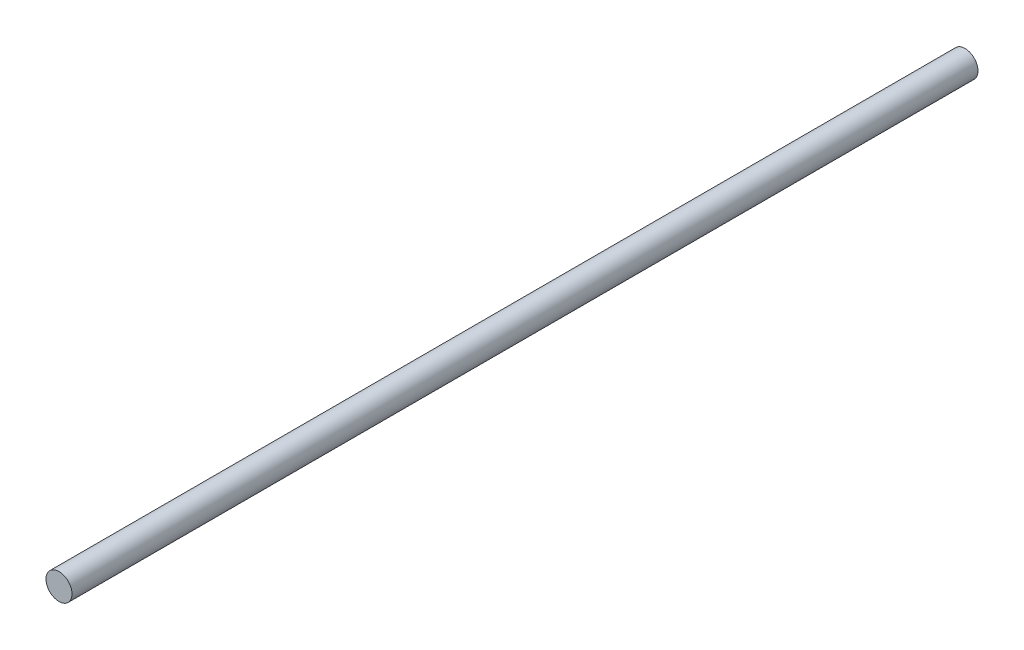
SolidWorks part; units mm, degrees
ref_plane "Front Plane" through (0, 0, 0) normal (0, 0, 1) x (1, 0, 0)
ref_plane "Top Plane" through (0, 0, 0) normal (0, 1, 0) x (1, 0, 0)
ref_plane "Right Plane" through (0, 0, 0) normal (1, 0, 0) x (0, 0, -1)
sketch "Sketch1" plane through (0, 0, 0) normal (0, 0, 1) x (1, 0, 0)
  circle A0 centre (0, 0) radius 6
  dimension "D1" = 12
extrude "Boss-Extrude1" add sketch "Sketch1" along normal mid plane 418
